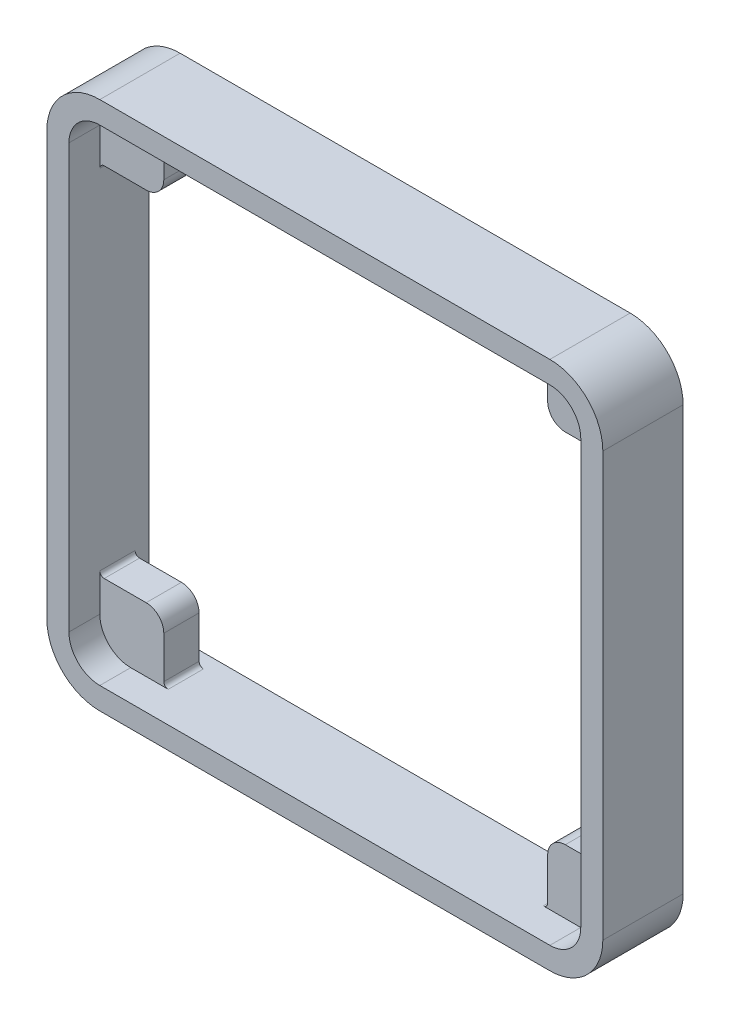
SolidWorks part; units mm, degrees
ref_plane "Front Plane" through (0, 0, 0) normal (1, 0, 0) x (0, 1, 0)
ref_plane "Top Plane" through (0, 0, 0) normal (0, 0, 1) x (0, 1, 0)
ref_plane "Right Plane" through (0, 0, 0) normal (0, 1, 0) x (-1, 0, 0)
sketch "Esquisse1" plane through (0, 0, -1424.6918) normal (0, 0, 1) x (1, 0, 0)
  line L4 (670.0024, 1197.1081) -> (670.0024, 1149.1081)
  line L5 (676.0024, 1143.1081) -> (727.0024, 1143.1081)
  line L6 (733.0024, 1149.1081) -> (733.0024, 1197.1081)
  line L7 (727.0024, 1203.1081) -> (676.0024, 1203.1081)
  line L8 (676.0024, 1145.6081) -> (727.0024, 1145.6081)
  line L9 (730.5024, 1149.1081) -> (730.5024, 1197.1081)
  line L10 (672.5024, 1197.1081) -> (672.5024, 1149.1081)
  line L11 (727.0024, 1200.6081) -> (676.0024, 1200.6081)
  line L12 (676.0024, 1145.6081) -> (727.0024, 1145.6081)
  line L13 (730.5024, 1149.1081) -> (730.5024, 1197.1081)
  line L14 (672.5024, 1197.1081) -> (672.5024, 1149.1081)
  line L15 (727.0024, 1200.6081) -> (676.0024, 1200.6081)
  arc A4 (676.0024, 1203.1081) -> (670.0024, 1197.1081) centre (676.0024, 1197.1081) ccw
  arc A5 (670.0024, 1149.1081) -> (676.0024, 1143.1081) centre (676.0024, 1149.1081) ccw
  arc A6 (727.0024, 1143.1081) -> (733.0024, 1149.1081) centre (727.0024, 1149.1081) ccw
  arc A7 (733.0024, 1197.1081) -> (727.0024, 1203.1081) centre (727.0024, 1197.1081) ccw
  arc A8 (672.5024, 1149.1081) -> (676.0024, 1145.6081) centre (676.0024, 1149.1081) ccw
  arc A9 (727.0024, 1145.6081) -> (730.5024, 1149.1081) centre (727.0024, 1149.1081) ccw
  arc A10 (730.5024, 1197.1081) -> (727.0024, 1200.6081) centre (727.0024, 1197.1081) ccw
  arc A11 (676.0024, 1200.6081) -> (672.5024, 1197.1081) centre (676.0024, 1197.1081) ccw
  arc A12 (672.5024, 1149.1081) -> (676.0024, 1145.6081) centre (676.0024, 1149.1081) ccw
  arc A13 (727.0024, 1145.6081) -> (730.5024, 1149.1081) centre (727.0024, 1149.1081) ccw
  arc A14 (730.5024, 1197.1081) -> (727.0024, 1200.6081) centre (727.0024, 1197.1081) ccw
  arc A15 (676.0024, 1200.6081) -> (672.5024, 1197.1081) centre (676.0024, 1197.1081) ccw
  dimension "D1" = 0.5
  dimension "D2" = 2.5
extrude "Boss.-Extru.1" add sketch "Esquisse1" along normal blind 7.5
sketch "Esquisse2" plane through (0, 0, -1424.6918) normal (0, 0, -1) x (1, 0, 0)
  line L0 (672.5024, -1152.8581) -> (679.7524, -1152.8581)
  line L1 (672.5024, -1197.1081) -> (672.5024, -1149.1081) construction
  line L2 (679.7524, -1152.8581) -> (679.7524, -1145.6081)
  line L3 (676.0024, -1145.6081) -> (727.0024, -1145.6081) construction
  line L4 (672.5024, -1152.8581) -> (672.5024, -1145.6081)
  line L5 (672.5024, -1145.6081) -> (679.7524, -1145.6081)
  line L7 (701.5024, -1145.6081) -> (701.5024, -1200.6081) construction
  line L8 (727.0024, -1200.6081) -> (676.0024, -1200.6081) construction
  line L9 (672.5024, -1173.1081) -> (730.5024, -1173.1081) construction
  line L10 (730.5024, -1149.1081) -> (730.5024, -1197.1081) construction
  line L11 (730.5024, -1152.8581) -> (723.2524, -1152.8581)
  line L12 (730.5024, -1152.8581) -> (730.5024, -1145.6081)
  line L13 (730.5024, -1145.6081) -> (723.2524, -1145.6081)
  line L14 (723.2524, -1152.8581) -> (723.2524, -1145.6081)
  line L15 (730.5024, -1193.3581) -> (723.2524, -1193.3581)
  line L16 (730.5024, -1193.3581) -> (730.5024, -1200.6081)
  line L17 (730.5024, -1200.6081) -> (723.2524, -1200.6081)
  line L18 (723.2524, -1193.3581) -> (723.2524, -1200.6081)
  line L19 (679.7524, -1193.3581) -> (679.7524, -1200.6081)
  line L20 (672.5024, -1200.6081) -> (679.7524, -1200.6081)
  line L21 (672.5024, -1193.3581) -> (672.5024, -1200.6081)
  line L22 (672.5024, -1193.3581) -> (679.7524, -1193.3581)
  dimension "D1" = 7.25
  dimension "D2" = 7.25
extrude "Boss.-Extru.2" add sketch "Esquisse2" against normal blind 4
fillet "Congé1" radius 2 4 edges at (723.2524, 1152.8581, -1422.6918) (723.2524, 1193.3581, -1422.6918) (679.7524, 1193.3581, -1422.6918) (679.7524, 1152.8581, -1422.6918)
fillet "Congé2" radius 0.5 8 edges at (723.2524, 1145.6081, -1422.6918) (730.5024, 1152.8581, -1422.6918) (723.2524, 1200.6081, -1422.6918) (730.5024, 1193.3581, -1422.6918) (679.7524, 1145.6081, -1422.6918) (672.5024, 1152.8581, -1422.6918) (672.5024, 1193.3581, -1422.6918) (679.7524, 1200.6081, -1422.6918)
extrude "Boss.-Extru.3" add sketch "Esquisse1<2>" against normal blind 1.6
sketch "Esquisse1<2>" plane through (0, 0, -1424.6918) normal (0, 0, 1) x (1, 0, 0) same geometry as "Esquisse1"
